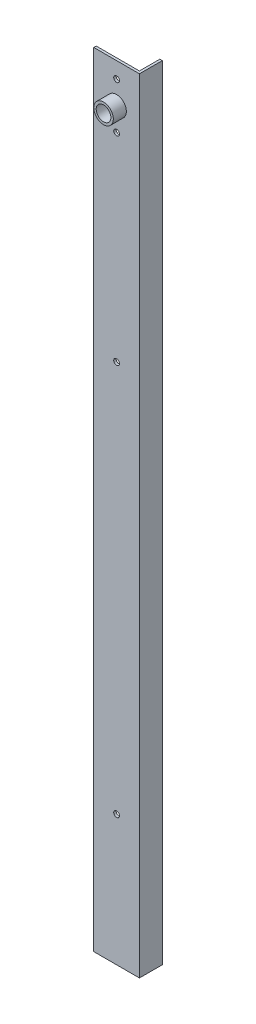
SolidWorks part; units mm, degrees
material "Galvanized Steel"
ref_plane "Front Plane" through (0, 0, 0) normal (0, 0, 1) x (1, 0, 0)
ref_plane "Top Plane" through (0, 0, 0) normal (0, 1, 0) x (1, 0, 0)
ref_plane "Right Plane" through (0, 0, 0) normal (1, 0, 0) x (0, 0, -1)
sketch "Sketch1" plane through (0, 0, 0) normal (0, 1, 0) x (1, 0, 0)
  line L1 (-44.45, -22.225) -> (44.45, -22.225)
  line L2 (-44.45, -22.225) -> (-44.45, 22.225)
  line L3 (-44.45, 22.225) -> (44.45, 22.225)
  line L4 (44.45, -22.225) -> (44.45, 22.225)
  line L5 (-44.45, -22.225) -> (44.45, 22.225) construction
  line L6 (-44.45, 22.225) -> (44.45, -22.225) construction
  point P0 (0, 0)
  dimension "D1" = 88.9
  dimension "D2" = 44.45
extrude "Boss-Extrude1" add sketch "Sketch1" along normal blind 1524
sketch "Sketch2" plane through (0, 0, 22.225) normal (0, 0, 1) x (1, 0, 0)
  line L0 (-44.45, 1524) -> (44.45, 1524) construction
  line L2 (0, 1402.7547) -> (0, 1492.8453) construction
  circle A0 centre (0, 1447.8) radius 7.9375
  circle A1 centre (0, 1492.8453) radius 5.588
  circle A2 centre (0, 1402.7547) radius 5.588
  point P5 (0, 1524)
  point P9 (0, 1447.8)
  dimension "D1" = 15.875
  dimension "D3" = 11.176
  dimension "D2" = 1447.8
  dimension "D4" = 90.0906
extrude "Cut-Extrude1" cut sketch "Sketch2" against normal up to next
sketch "Sketch4" plane through (0, 0, 22.225) normal (0, 0, 1) x (1, 0, 0)
  circle A0 centre (0, 1447.8) radius 14.2875
  circle A1 centre (0, 1447.8) radius 19.05
  dimension "D1" = 38.1
  dimension "D2" = 28.575
extrude "Boss-Extrude2" add sketch "Sketch4" along normal blind 25.4
sketch "Sketch5" plane through (0, 1524, 0) normal (0, 1, 0) x (1, 0, 0)
  line L8 (39.6875, 17.4625) -> (39.6875, 22.225)
  line L9 (44.45, 22.225) -> (-44.45, 22.225) construction
  line L10 (39.6875, 22.225) -> (-44.45, 22.225)
  line L11 (-44.45, 22.225) -> (-44.45, -17.4625)
  line L12 (39.6875, -17.4625) -> (39.6875, 17.4625)
  line L13 (39.6875, 17.4625) -> (-39.6875, 17.4625)
  line L14 (-39.6875, 17.4625) -> (-39.6875, -17.4625)
  line L15 (-39.6875, -17.4625) -> (39.6875, -17.4625)
  line L16 (39.6875, -17.4625) -> (39.6875, 17.4625)
  line L19 (-39.6875, -17.4625) -> (39.6875, -17.4625)
  line L20 (-44.45, 22.225) -> (-44.45, -22.225) construction
  line L21 (-44.45, -17.4625) -> (-39.6875, -17.4625)
  dimension "D1" = 4.7625
extrude "Cut-Extrude2" cut sketch "Sketch5" against normal up to next
sketch "Sketch6" plane through (0, 0, 0) normal (0, -1, 0) x (1, 0, 0)
  line L1 (44.45, -22.225) -> (-44.45, -22.225)
  line L2 (44.45, -22.225) -> (44.45, 22.225)
  line L3 (44.45, 22.225) -> (-44.45, 22.225)
  line L4 (-44.45, -22.225) -> (-44.45, 22.225)
extrude "Boss-Extrude3" add sketch "Sketch6" against normal blind 6.35
sketch "Sketch7" plane through (0, 0, 22.225) normal (0, 0, 1) x (1, 0, 0)
  line L0 (-44.45, 1524) -> (44.45, 1524) construction
  line L1 (-44.45, 0) -> (44.45, 0) construction
  circle A0 centre (0, 1016) radius 5.588
  circle A1 centre (0, 254) radius 5.588
  point P7 (0, 1524)
  dimension "D1" = 11.176
  dimension "D2" = 508
  dimension "D3" = 254
extrude "Cut-Extrude3" cut sketch "Sketch7" against normal through all
